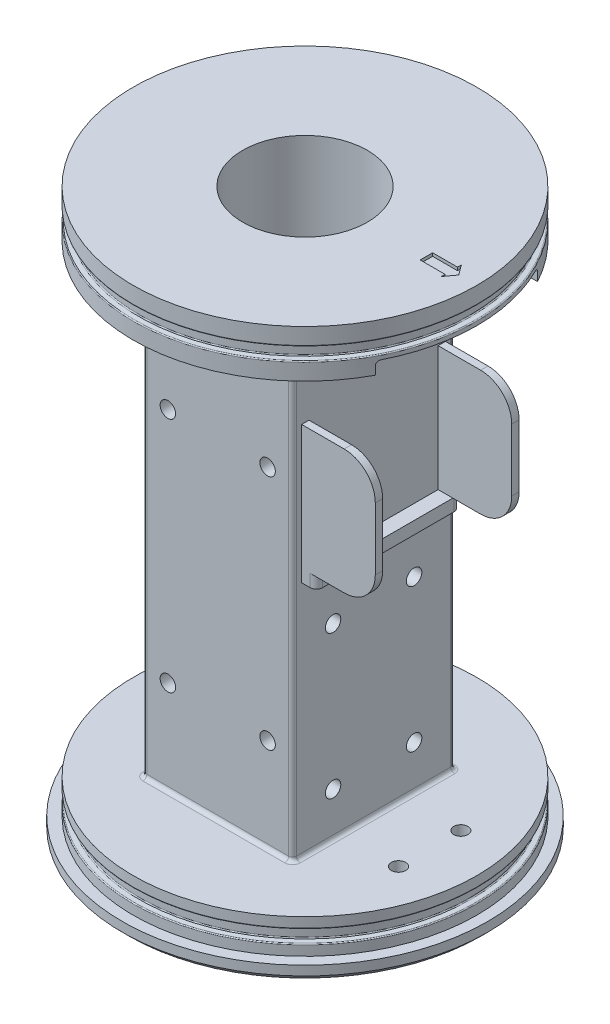
SolidWorks part; units mm, degrees
ref_plane "Front Plane" through (0, 0, 0) normal (0, 0, 1) x (1, 0, 0)
ref_plane "Top Plane" through (0, 0, 0) normal (0, 1, 0) x (1, 0, 0)
ref_plane "Right Plane" through (0, 0, 0) normal (1, 0, 0) x (0, 0, -1)
sketch "Sketch1" plane through (0, 0, 0) normal (0, 1, 0) x (1, 0, 0)
  line L1 (-16.51, -16.51) -> (16.51, -16.51)
  line L2 (-16.51, -16.51) -> (-16.51, 16.51)
  line L3 (-16.51, 16.51) -> (16.51, 16.51)
  line L4 (16.51, -16.51) -> (16.51, 16.51)
  line L5 (-16.51, -16.51) -> (16.51, 16.51) construction
  line L6 (-16.51, 16.51) -> (16.51, -16.51) construction
  point P0 (0, 0)
  dimension "D1" = 33.02
  dimension "D2" = 33.02
extrude "Boss-Extrude1" add sketch "Sketch1" along normal blind 114.3
sketch "Sketch3" plane through (0, 0, 0) normal (0, 0, 1) x (1, 0, 0)
  line L0 (0, 0) -> (0, 114.3) construction
  line L1 (-16.51, 0) -> (16.51, 0) construction
  line L2 (-16.51, 114.3) -> (16.51, 114.3) construction
  line L3 (0, 114.3) -> (-35, 114.3)
  line L4 (-35, 114.3) -> (-35, 110.7877)
  line L5 (-35, 104.648) -> (0, 104.648)
  line L6 (0, 104.648) -> (0, 114.3)
  line L7 (0, 0) -> (-37.211, 0)
  line L8 (-37.211, 0) -> (-37.211, 3.175)
  line L9 (-35, 10.16) -> (0, 10.16)
  line L10 (0, 10.16) -> (0, 0)
  line L11 (-35, 110.7877) -> (-33.7, 110.674)
  line L12 (-33.7, 110.674) -> (-33.7, 108.274)
  line L13 (-33.7, 108.274) -> (-35, 108.1603)
  line L14 (-35, 108.1603) -> (-35, 104.648)
  line L17 (-33.7, 5.4675) -> (-35, 5.3538)
  line L22 (-35, 10.16) -> (-35, 7.9812)
  line L23 (-35, 7.9812) -> (-33.7, 7.8675)
  line L24 (-33.7, 7.8675) -> (-33.7, 5.4675)
  line L25 (-35, 5.3538) -> (-35, 3.175)
  line L26 (-35, 3.175) -> (-37.211, 3.175)
  dimension "D1" = 9.652
  dimension "D2" = 67.4
  dimension "D3" = 70
  dimension "D4" = 10.16
  dimension "D5" = 95
  dimension "D6" = 74.422
  dimension "D7" = 95
  dimension "D8" = 95
  dimension "D9" = 2.4
  dimension "D10" = 3.175
  dimension "D11" = 95
revolve "Revolve1" add sketch "Sketch3" angle 360 about L0
sketch "Sketch5" plane through (0, 0, 0) normal (0, 0, 1) x (1, 0, 0)
  line L0 (0, 0) -> (0, 114.3) construction
  line L1 (35, 114.3) -> (-35, 114.3) construction
  line L4 (-37.211, 0) -> (37.211, 0) construction
  line L5 (-12.7, 114.3) -> (0, 114.3)
  line L7 (0, 0) -> (-12.7, 0)
  line L8 (0, 114.3) -> (0, 0)
  line L9 (-12.7, 114.3) -> (-12.7, 0)
  dimension "D1" = 25.4
revolve "Cut-Revolve1" cut sketch "Sketch5" angle 360 about L0
sketch "Sketch6" plane through (0, 114.3, 0) normal (0, 1, 0) x (1, 0, 0)
  line L7 (24.7275, 1.27) -> (24.7275, -1.27)
  line L10 (24.7275, 1.27) -> (29.8075, 1.27)
  line L11 (29.8075, 1.27) -> (29.8075, 2.0443)
  line L12 (24.7275, -1.27) -> (29.8075, -1.27)
  line L13 (29.8075, 2.0443) -> (31.3149, 0)
  line L14 (31.3149, 0) -> (29.8075, -2.0443)
  line L15 (29.8075, -2.0443) -> (29.8075, -1.27)
  point P0 (0, 0)
  point P1 (24.7275, 0)
  point P10 (31.0111, 0)
  dimension "D1" = 2.54
  dimension "D2" = 2.54
  dimension "D3" = 5.08
extrude "Cut-Extrude1" cut sketch "Sketch6" against normal blind 0.635
sketch "Sketch9" plane through (-16.51, 0, 0) normal (-1, 0, 0) x (0, 0, 1)
  line L0 (16.51, 10.16) -> (-16.51, 10.16) construction
  circle A0 centre (-8.89, 80.645) radius 1.575
  circle A1 centre (8.89, 80.645) radius 1.575
  circle A2 centre (-8.89, 34.925) radius 1.575
  circle A3 centre (8.89, 34.925) radius 1.575
  dimension "D1" = 3.15
  dimension "D2" = 45.72
  dimension "D3" = 17.78
  dimension "D4" = 24.765
  dimension "D5" = 8.89
extrude "feather_holes" cut sketch "Sketch9" against normal blind 5
sketch "Sketch10" plane through (0, 0, -16.51) normal (0, 0, -1) x (-1, 0, 0)
  line L1 (16.51, 10.16) -> (-16.51, 10.16) construction
  line L2 (-16.51, 104.648) -> (16.51, 104.648) construction
  circle A0 centre (-8.89, 94.488) radius 1.575
  circle A1 centre (11.43, 94.488) radius 1.575
  circle A2 centre (-8.89, 74.168) radius 1.575
  circle A3 centre (11.43, 74.168) radius 1.575
  circle A4 centre (-8.89, 33.02) radius 1.575
  circle A5 centre (11.43, 33.02) radius 1.575
  circle A6 centre (-8.89, 20.32) radius 1.575
  circle A7 centre (11.43, 20.32) radius 1.575
  circle A8 centre (11.43, 63.5) radius 1.575
  circle A9 centre (11.43, 48.26) radius 1.575
  circle A10 centre (-8.89, 63.5) radius 1.575
  circle A11 centre (-8.89, 48.26) radius 1.575
  dimension "D9" = 3.15
  dimension "D10" = 20.32
  dimension "D1" = 20.32
  dimension "D2" = 20.32
  dimension "D3" = 12.7
  dimension "D4" = 20.32
  dimension "D5" = 8.89
  dimension "D6" = 8.89
  dimension "D7" = 10.16
  dimension "D8" = 10.16
  dimension "D11" = 15.24
  dimension "D12" = 38.1
  dimension "D13" = 8.89
extrude "sensor_holes" cut sketch "Sketch10" against normal blind 5
sketch "Sketch15" plane through (16.51, 0, 0) normal (1, 0, 0) x (0, 0, -1)
  line L0 (16.51, 10.16) -> (-16.51, 10.16) construction
  line L1 (16.51, 10.16) -> (-16.51, 10.16)
  line L2 (16.51, 10.16) -> (16.51, 104.648)
  line L3 (16.51, 104.648) -> (-16.51, 104.648)
  line L4 (-16.51, 10.16) -> (-16.51, 104.648)
  line L5 (16.51, 10.16) -> (-16.51, 104.648) construction
  line L6 (16.51, 104.648) -> (-16.51, 10.16) construction
  line L7 (-16.51, 104.648) -> (16.51, 104.648) construction
  point P0 (0, 57.404)
  dimension "D1" = 33.02
  dimension "D2" = 0
extrude "Cut-Extrude7" cut sketch "Sketch15" against normal blind 2.54
sketch "Sketch13" plane through (0, 0, 16.51) normal (0, 0, 1) x (1, 0, 0)
  line L1 (13.97, 10.16) -> (-16.51, 10.16) construction
  circle A0 centre (-11.43, 77.47) radius 1.575
  circle A1 centre (8.89, 77.47) radius 1.575
  circle A2 centre (-11.43, 29.21) radius 1.575
  circle A3 centre (8.89, 29.21) radius 1.575
  dimension "D4" = 3.15
  dimension "D1" = 48.26
  dimension "D2" = 20.32
  dimension "D3" = 11.43
  dimension "D6" = 19.05
extrude "li_battery_holes" cut sketch "Sketch13" against normal blind 5
sketch "Sketch14" plane through (0, 0, -16.51) normal (0, 0, -1) x (-1, 0, 0)
  line L0 (3.6886, 94.107) -> (-1.27, 94.107)
  line L17 (-1.27, 74.549) -> (3.6886, 74.549)
  arc A0 (-1.27, 94.107) -> (-1.27, 74.549) centre (-1.27, 84.328) ccw
  arc A4 (-2.8783, 77.082) -> (-2.8783, 91.574) centre (3.6886, 84.328) ccw
  arc A5 (3.6886, 74.549) -> (3.6886, 94.107) centre (3.6886, 84.328) ccw
  dimension "D3" = 19.558
  dimension "D1" = 2.54
  dimension "D2" = 4.9586
extrude "Cut-Extrude6" cut sketch "Sketch14" against normal blind 2.794
fillet "Fillet8" radius 0.2 8 edges at (35, 108.1603, 0) (33.7, 108.274, 0) (33.7, 110.674, 0) (35, 110.7877, 0) (35, 7.9812, 0) (35, 5.3538, 0) (33.7, 5.4675, 0) (33.7, 7.8675, 0)
chamfer "Chamfer1" distance 1.27 angle 45 1 edges at (37.211, 0, 0)
sketch "Sketch19" plane through (0, 0, 0) normal (0, -1, 0) x (1, 0, 0)
  circle A0 centre (25.4, -6.35) radius 1.45
  circle A1 centre (25.4, 6.35) radius 1.45
  dimension "D2" = 2.9
  dimension "D1" = 25.4
  dimension "D3" = 12.7
  dimension "D4" = 6.35
extrude "Cut-Extrude8" cut sketch "Sketch19" against normal up to next
sketch "Sketch21" plane through (0, 104.648, 0) normal (0, -1, 0) x (1, 0, 0)
  line L0 (13.97, -16.51) -> (13.97, 16.51) construction
  line L1 (13.97, -16.51) -> (13.97, 16.51)
  line L2 (13.97, 16.51) -> (30.8613, 16.51)
  line L3 (13.97, -16.51) -> (30.8613, -16.51)
  circle A1 centre (0, 0) radius 35
  arc A2 (30.8613, -16.51) -> (30.8613, 16.51) centre (0, 0) ccw
  dimension "D1" = 0
extrude "Cut-Extrude10" cut sketch "Sketch21" against normal blind 2.54
sketch "Sketch20" plane through (13.97, 0, 0) normal (1, 0, 0) x (0, 0, -1)
  line L0 (35, 10.16) -> (-35, 10.16) construction
  circle A0 centre (-8.255, 48.26) radius 1.575
  circle A1 centre (8.255, 48.26) radius 1.575
  circle A2 centre (-8.255, 19.05) radius 1.575
  circle A3 centre (8.255, 19.05) radius 1.575
  dimension "D1" = 3.15
  dimension "D2" = 29.21
  dimension "D3" = 16.51
  dimension "D4" = 8.89
  dimension "D5" = 8.255
extrude "Cut-Extrude9" cut sketch "Sketch20" against normal blind 2.968
sketch "Sketch23" plane through (13.97, 0, 0) normal (1, 0, 0) x (0, 0, -1)
  line L0 (-14.65, 86.588) -> (-14.65, 61.188)
  line L1 (-14.65, 61.188) -> (-13.15, 61.188)
  line L2 (-13.15, 61.188) -> (-13.15, 86.588)
  line L3 (-13.15, 86.588) -> (-14.65, 86.588)
  line L4 (13.15, 86.588) -> (13.15, 61.188)
  line L5 (13.15, 61.188) -> (14.65, 61.188)
  line L6 (14.65, 61.188) -> (14.65, 86.588)
  line L7 (14.65, 86.588) -> (13.15, 86.588)
  line L9 (-16.51, 107.188) -> (16.51, 107.188) construction
  point P14 (0, 107.188)
  dimension "D1" = 1.5
  dimension "D2" = 26.3
  dimension "D3" = 13.15
  dimension "D4" = 46
  dimension "D5" = 25.4
extrude "Boss-Extrude3" add sketch "Sketch23" along normal blind 15
sketch "Sketch24" plane through (0, 61.188, 0) normal (0, -1, 0) x (1, 0, 0)
  line L1 (13.97, 14.65) -> (15.7, 14.65)
  line L2 (13.97, -14.65) -> (13.97, 14.65)
  line L3 (28.97, 14.65) -> (13.97, 14.65) construction
  line L4 (16.97, 13.38) -> (16.97, -13.38)
  line L5 (28.97, -14.65) -> (13.97, -14.65) construction
  line L6 (15.7, -14.65) -> (13.97, -14.65)
  arc A0 (15.7, -14.65) -> (16.97, -13.38) centre (15.7, -13.38) ccw
  arc A1 (15.7, 14.65) -> (16.97, 13.38) centre (15.7, 13.38) cw
  point P11 (16.97, -14.65)
  point P14 (16.97, 14.65)
  dimension "D2" = 1.27
  dimension "D1" = 3
extrude "Boss-Extrude4" add sketch "Sketch24" along normal blind 2.54
fillet "Fillet1" radius 0.7937 4 edges at (-16.51, 57.404, 16.51) (-16.51, 57.404, -16.51) (13.97, 57.404, -16.51) (13.97, 57.404, 16.51)
fillet "Fillet11" radius 0.7937 2 edges at (13.97, 105.918, 16.51) (13.97, 105.918, -16.51)
fillet "Fillet12" radius 0.7937 20 edges at (-16.2775, 10.16, -16.2775) (-16.51, 10.16, 0) (-16.2775, 10.16, 16.2775) (-1.27, 10.16, 16.51) (13.7375, 10.16, 16.2775) (13.97, 10.16, 0) (13.7375, 10.16, -16.2775) (13.7375, 104.648, -16.2775) (13.7375, 104.648, 16.2775) (-1.27, 104.648, 16.51) (-16.2775, 104.648, 16.2775) (-16.51, 104.648, 0) (-16.2775, 104.648, -16.2775) (22.8125, 107.188, 16.51) (14.2025, 107.188, 16.2775) (13.97, 107.188, 0) (14.2025, 107.188, -16.2775) (-1.27, 10.16, -16.51) (-1.27, 104.648, -16.51) (22.8125, 107.188, -16.51)
fillet "Fillet13" radius 6.35 4 edges at (28.97, 61.188, -13.9) (28.97, 61.188, 13.9) (28.97, 86.588, -13.9) (28.97, 86.588, 13.9)
